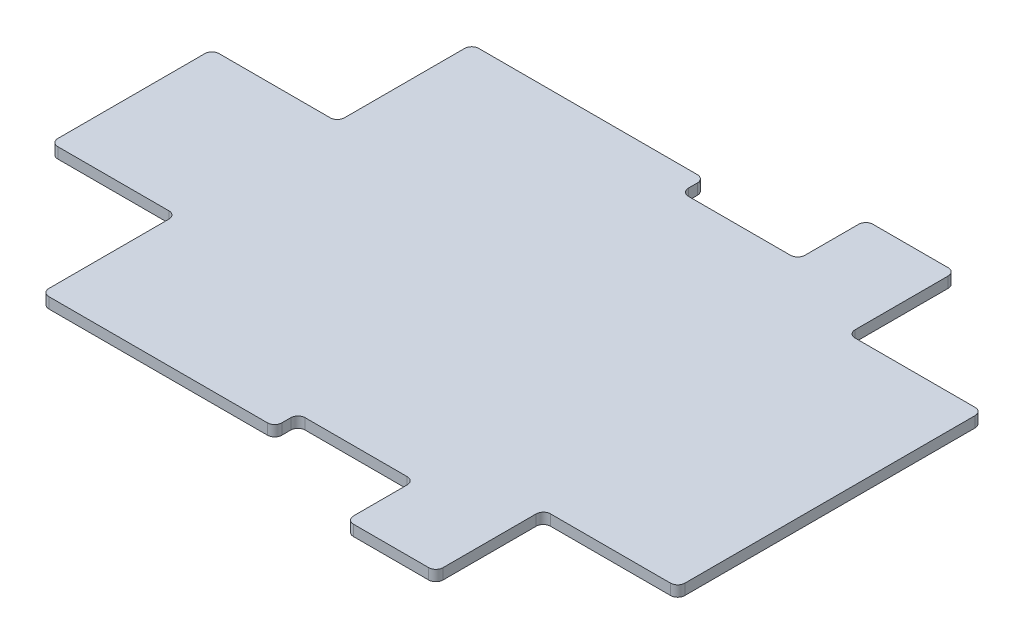
SolidWorks part; units mm, degrees
material "Aleación 1060"
ref_plane "Alzado" through (0, 0, 0) normal (0, 0, 1) x (1, 0, 0)
ref_plane "Planta" through (0, 0, 0) normal (0, 1, 0) x (1, 0, 0)
ref_plane "Vista lateral" through (0, 0, 0) normal (1, 0, 0) x (0, 0, -1)
sketch "Croquis1" plane through (0, 0, 0) normal (0, 1, 0) x (1, 0, 0)
  line L0 (0, 0) -> (-390, 0)
  line L1 (-390, 0) -> (-390, 45)
  line L2 (-390, 45) -> (-320, 45)
  line L3 (-320, 45) -> (-320, 120)
  line L4 (-320, 120) -> (-190, 120)
  line L5 (-190, 120) -> (-190, 107)
  line L6 (-190, 107) -> (-125, 107)
  line L7 (-125, 107) -> (-125, 145)
  line L8 (-125, 145) -> (-75, 145)
  line L9 (-75, 145) -> (-75, 85)
  line L10 (0, 0) -> (0, 85)
  line L11 (0, 85) -> (-75, 85)
  dimension "D1" = 390
  dimension "D2" = 45
  dimension "D3" = 75
  dimension "D4" = 120
  dimension "D5" = 130
  dimension "D6" = 13
  dimension "D7" = 50
  dimension "D8" = 85
  dimension "D9" = 65
  dimension "D10" = 60
extrude "Saliente-Extruir1" add sketch "Croquis1" along normal blind 6
mirror "Simetría1" about plane through (0, 6, 0) normal (0, 0, -1) of "Saliente-Extruir1"
fillet "Redondeo1" radius 4 20 edges at (-390, 3, -45) (-320, 3, -45) (-320, 3, -120) (-190, 3, -120) (-190, 3, -107) (-125, 3, -107) (-125, 3, -145) (-75, 3, -85) (-75, 3, -145) (0, 3, -85) (0, 3, 85) (-75, 3, 85) (-75, 3, 145) (-125, 3, 145) (-125, 3, 107) (-190, 3, 107) (-190, 3, 120) (-320, 3, 120) (-320, 3, 45) (-390, 3, 45)
sketch "Croquis2" plane through (0, 6, 0) normal (0, 1, 0) x (1, 0, 0)
  line L0 (-390, 0) -> (0, 0) construction
  line L1 (-390, 41) -> (-390, -41) construction
  line L2 (0, -81) -> (0, 81) construction
  line L3 (-214.7209, -131) -> (31.1095, -131) construction
  line L4 (-214.0485, -154) -> (44.3152, -154) construction
  line L5 (-79, -145) -> (-121, -145) construction
  line L6 (-44, -177) -> (-156, -177)
  line L7 (-44, -177) -> (-44, -131)
  line L8 (-44, -131) -> (-156, -131)
  line L9 (-156, -177) -> (-156, -131)
  line L10 (-44, -177) -> (-156, -131) construction
  line L11 (-44, -131) -> (-156, -177) construction
  line L12 (-156, 154) -> (-44, 154) construction
  line L13 (-374, -177) -> (-486, -177)
  line L14 (-374, -177) -> (-374, -131)
  line L15 (-374, -131) -> (-486, -131)
  line L16 (-486, -177) -> (-486, -131)
  line L17 (-374, -177) -> (-486, -131) construction
  line L18 (-374, -131) -> (-486, -177) construction
  line L19 (-44, 177) -> (-156, 177)
  line L20 (-44, 177) -> (-44, 131)
  line L21 (-44, 131) -> (-156, 131)
  line L22 (-156, 177) -> (-156, 131)
  line L23 (-374, 131) -> (-486, 177) construction
  line L24 (-374, 177) -> (-486, 131) construction
  line L25 (-486, 177) -> (-486, 131)
  line L26 (-374, 131) -> (-486, 131)
  line L27 (-374, 177) -> (-374, 131)
  line L28 (-374, 177) -> (-486, 177)
  line L29 (-430, -154) -> (-430, 154) construction
  point P10 (-100, -154)
  point P17 (-100, -145)
  point P20 (-430, -154)
  point P33 (-430, 154)
  dimension "D1" = 131
  dimension "D2" = 154
  dimension "D3" = 46
  dimension "D4" = 112
  dimension "D5" = 330
  dimension "D6" = 308
sketch "Croquis3" plane through (0, 6, 0) normal (0, 1, 0) x (1, 0, 0)
  line L0 (-100, -145) -> (-100, 145) construction
  line L1 (-79, -145) -> (-121, -145) construction
  line L2 (-79, 145) -> (-121, 145) construction
  line L3 (-161.61, 16.8885) -> (-161.61, -25.475) construction
  line L4 (-232.2, 27.5722) -> (-232.2, -25.475) construction
  dimension "D1" = 132.2
  dimension "D2" = 61.61
ref_plane "Plano1" [suppressed] through (-430, 0, 0) normal (1, 0, 0) x (0, 0, -1)
